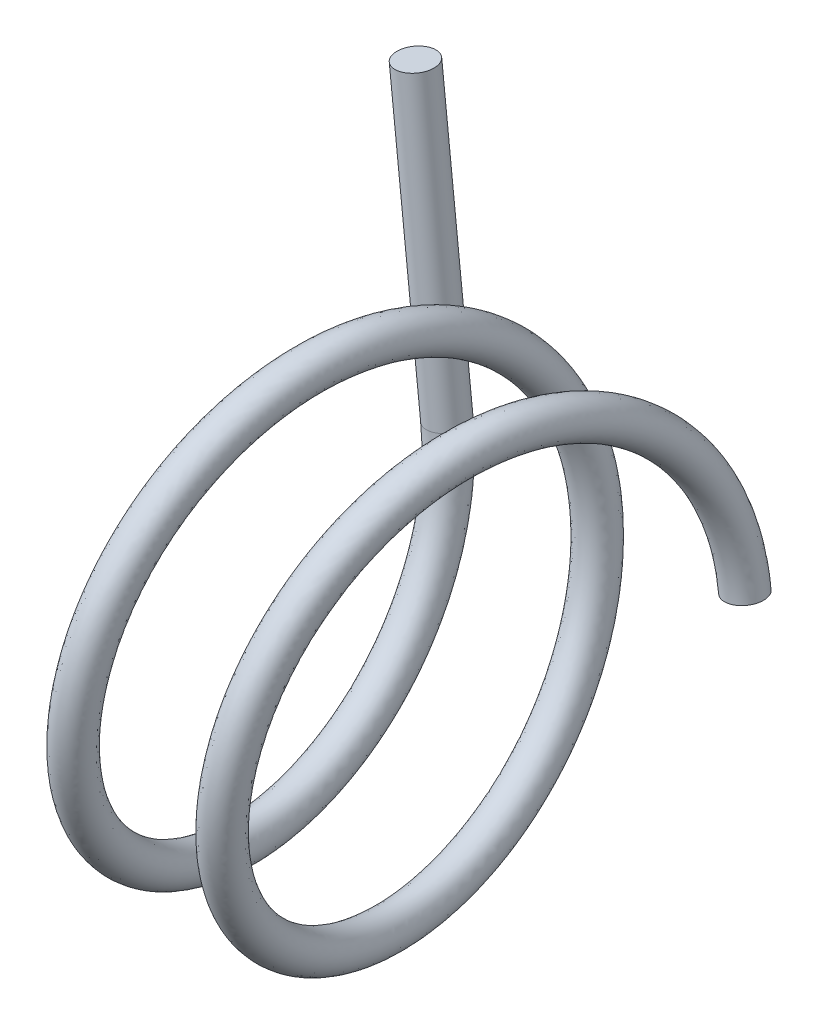
SolidWorks part; units mm, degrees
note: '?' marks a value the reader was unsure of.
ref_plane "Front Plane" through (0, 0, 0) normal (0, 0, 1) x (1, 0, 0)
ref_plane "Top Plane" through (0, 0, 0) normal (0, 1, 0) x (1, 0, 0)
ref_plane "Right Plane" through (0, 0, 0) normal (1, 0, 0) x (0, 0, -1)
sketch "Sketch2" plane through (0, 0, 0) normal (1, 0, 0) x (0, 0, -1)
  circle A0 centre (0, 0) radius 38.1
  dimension "D1" = 76.2
curve "Helix/Spiral1" pitch 25.4 height 50.8 turns 2
sweep "Sweep1" add path "Helix/Spiral1" circular profile diameter 6.35 parameters "D3"=6.35
other "CPoint1" parameters "Diameter"=6.35, "StubLength"=28.575
ref_axis "Axis1" through (51.8551, -9.9442, -38.1) along (-0.1055, 0.9944, 0)?
sketch "Sketch11" plane through (0, 0, 0) normal (-0.1055, 0.9944, 0) x (0.9944, 0.1055, 0)
  circle A1 centre (0, 38.1) radius 3.175
  circle A2 centre (0, 38.1) radius 3.175
  dimension "D1" = 0
extrude "Boss-Extrude1" add sketch "Sketch11" along normal blind 50.8
